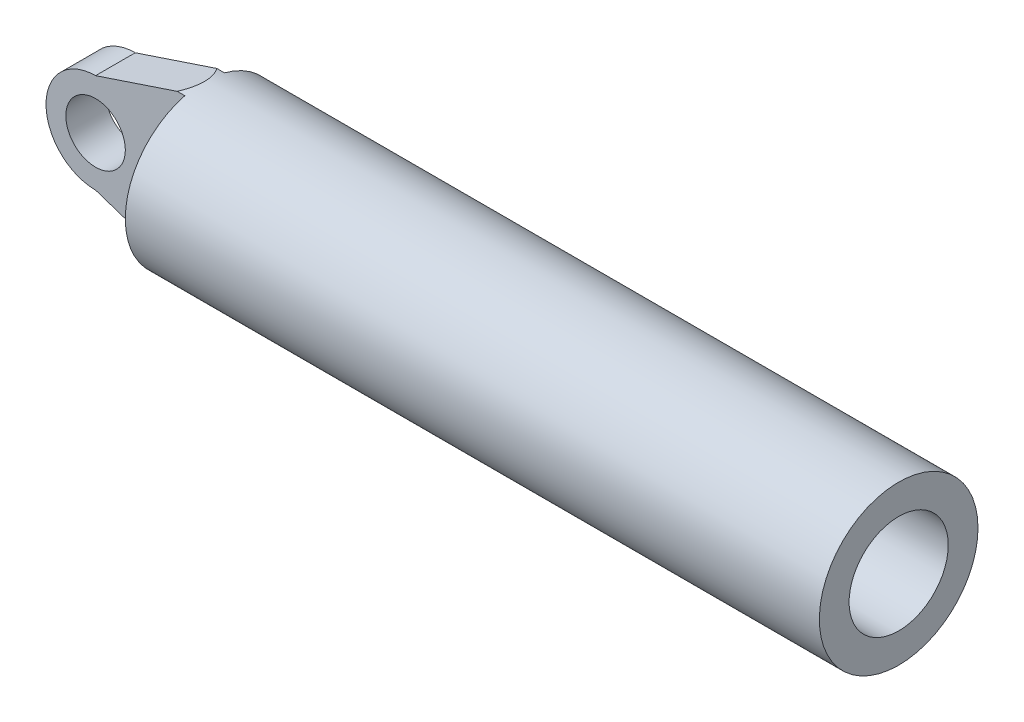
SolidWorks part; units mm, degrees
ref_plane "Front Plane" through (0, 0, 0) normal (0, 0, 1) x (1, 0, 0)
ref_plane "Top Plane" through (0, 0, 0) normal (0, 1, 0) x (1, 0, 0)
ref_plane "Right Plane" through (0, 0, 0) normal (1, 0, 0) x (0, 0, -1)
sketch "Sketch1" plane through (0, 0, 0) normal (1, 0, 0) x (0, 0, -1)
  circle A1 centre (0, 0) radius 40
  dimension "D2" = 80
extrude "Boss-Extrude1" add sketch "Sketch1" along normal blind 350
shell "Shell1" thickness 15 removed face at (350, 0, -40)
sketch "Sketch3" plane through (0, 0, 0) normal (0, 0, 1) x (1, 0, 0)
  line L0 (0, 40) -> (-45, 25)
  line L1 (-45, -25) -> (0, -40)
  line L2 (0, 40) -> (0, -40)
  circle A0 centre (-45, 0) radius 15
  arc A1 (-45, 25) -> (-45, -25) centre (-45, 0) ccw
  dimension "D1" = 30
extrude "Boss-Extrude2" add sketch "Sketch3" along normal blind 10 and the other way blind 10
sketch "Sketch4" plane through (0, 0, 0) normal (1, 0, 0) x (0, 0, -1)
  circle A0 centre (0, 0) radius 40
  circle A1 centre (0, 0) radius 50.168
extrude "Cut-Extrude1" cut sketch "Sketch4" against normal blind 68
